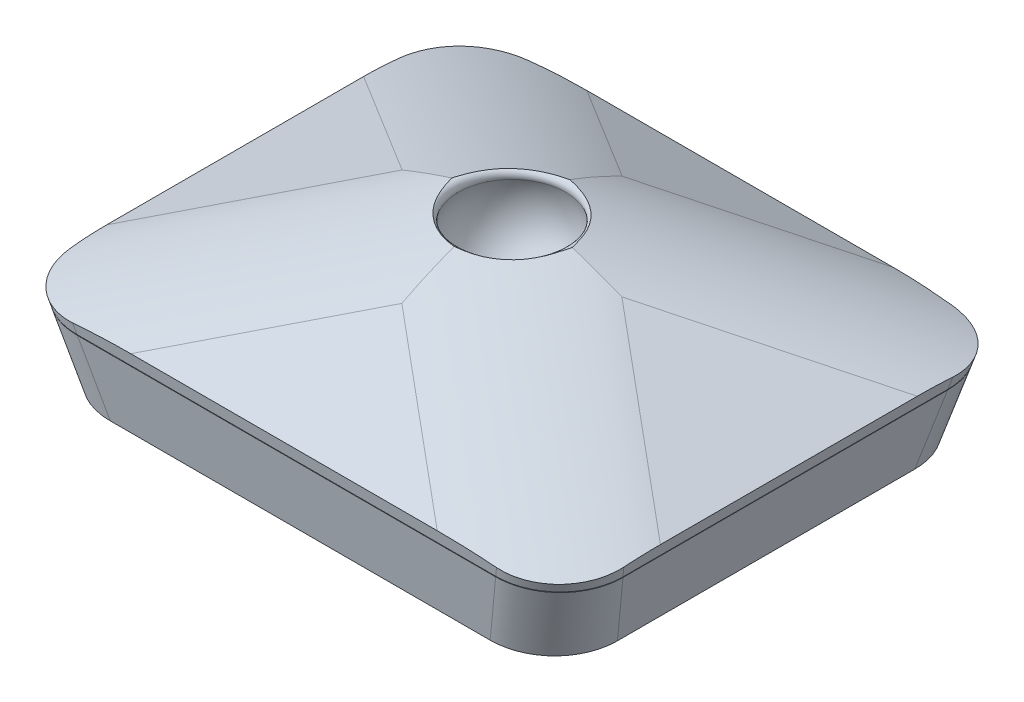
SolidWorks part; units mm, degrees
ref_plane "Front Plane" through (0, 0, 0) normal (0, 0, 1) x (1, 0, 0)
ref_plane "Top Plane" through (0, 0, 0) normal (0, 1, 0) x (1, 0, 0)
ref_plane "Right Plane" through (0, 0, 0) normal (1, 0, 0) x (0, 0, -1)
sketch "Sketch1" plane through (0, 0, 0) normal (0, 1, 0) x (1, 0, 0)
  line L1 (-42.5, 35) -> (42.5, 35)
  line L2 (-42.5, 35) -> (-42.5, -35)
  line L3 (-42.5, -35) -> (42.5, -35)
  line L4 (42.5, 35) -> (42.5, -35)
  line L5 (-42.5, 35) -> (42.5, -35) construction
  line L6 (-42.5, -35) -> (42.5, 35) construction
  point P0 (0, 0)
extrude "Boss-Extrude1" add sketch "Sketch1" along normal blind 26
sketch "Sketch2" plane through (0, 0, 35) normal (0, 0, 1) x (1, 0, 0)
  line L0 (-39, 0) -> (-42.5, 0)
  line L1 (-42.5, 0) -> (42.5, 0) construction
  line L2 (39, 0) -> (42.5, 0)
  line L4 (42.5, 26) -> (42.5, 0) construction
  line L5 (-42.5, 26) -> (-42.5, 0) construction
  line L6 (-42.5, 13) -> (-39, 0)
  line L7 (-42.5, 0) -> (-42.5, 13)
  line L8 (42.5, 13) -> (39, 0)
  line L9 (42.5, 0) -> (42.5, 13)
extrude "Cut-Extrude1" cut sketch "Sketch2" against normal through all
sketch "Sketch3" plane through (0, 0, 35) normal (0, 0, 1) x (1, 0, 0)
  line L0 (-10, 26) -> (-42.5, 13)
  line L1 (-42.5, 26) -> (42.5, 26) construction
  line L3 (-42.5, 13) -> (-42.5, 26)
  line L4 (-42.5, 26) -> (-10, 26)
  line L5 (10, 26) -> (42.5, 13)
  line L6 (42.5, 13) -> (42.5, 26)
  line L7 (42.5, 26) -> (10, 26)
extrude "Cut-Extrude2" cut sketch "Sketch3" against normal through all
sketch "Sketch4" plane through (0, 0, 0) normal (1, 0, 0) x (0, 0, -1)
  line L0 (32.5, 0) -> (35, 13)
  line L1 (35, 0) -> (-35, 0) construction
  line L3 (35, 13) -> (35, 0)
  line L4 (35, 0) -> (32.5, 0)
  line L5 (-32.5, 0) -> (-35, 13)
  line L6 (-35, 13) -> (-35, 0)
  line L7 (-35, 0) -> (-32.5, 0)
extrude "Cut-Extrude3" cut sketch "Sketch4" against normal through all and the other way through all
sketch "Sketch5" plane through (0, 0, 0) normal (1, 0, 0) x (0, 0, -1)
  line L0 (10, 26) -> (35, 13)
  line L1 (35, 26) -> (-35, 26) construction
  line L3 (35, 13) -> (35, 26)
  line L4 (35, 26) -> (10, 26)
  line L5 (-10, 26) -> (-35, 13)
  line L6 (-35, 13) -> (-35, 26)
  line L7 (-35, 26) -> (-10, 26)
extrude "Cut-Extrude4" cut sketch "Sketch5" against normal through all and the other way through all
sketch "Sketch7" plane through (0, 26, 0) normal (0, 1, 0) x (1, 0, 0)
  line L1 (-2.5, 2.5) -> (2.5, 2.5)
  line L2 (-2.5, 2.5) -> (-2.5, -2.5)
  line L3 (-2.5, -2.5) -> (2.5, -2.5)
  line L4 (2.5, 2.5) -> (2.5, -2.5)
  line L5 (-2.5, 2.5) -> (2.5, -2.5) construction
  line L6 (-2.5, -2.5) -> (2.5, 2.5) construction
  point P0 (0, 0)
extrude "Cut-Extrude5" cut sketch "Sketch7" against normal blind 5
sketch "Sketch8" plane through (0, 21, 0) normal (0, 1, 0) x (1, 0, 0)
  line L0 (-17.1014, 0) -> (19.9364, 0) construction
  line L1 (-9, 0) -> (9, 0)
  arc A0 (9, 0) -> (-9, 0) centre (0, 0) ccw
revolve "Cut-Revolve3" cut sketch "Sketch8" angle 360 about L0
fillet "Fillet1" radius 40 4 edges at (26.25, 19.5, -22.5) (-26.25, 19.5, -22.5) (-26.25, 19.5, 22.5) (26.25, 19.5, 22.5)
fillet "Fillet2" radius 10 4 edges at (-40.5078, 5.6003, -33.577) (40.5078, 5.6003, -33.577) (40.5078, 5.6003, 33.577) (-40.5078, 5.6003, 33.577)
fillet "Fillet3" radius 1 1 edges at (0, 26, 7.4833)
sketch "Sketch10" plane through (0, 0, 0) normal (0, -1, 0) x (1, 0, 0)
  line L0 (-29.1523, 31.8032) -> (29.1523, 31.8032)
  line L1 (-38.1307, 22.8167) -> (-38.1307, -22.8167)
  line L2 (29.1523, -31.8032) -> (-29.1523, -31.8032)
  line L3 (38.1307, -22.8167) -> (38.1307, 22.8167)
  arc A0 (-29.1523, 31.8032) -> (-38.1307, 22.8167) centre (-28.6439, 22.3168) ccw
  arc A1 (-38.1307, -22.8167) -> (-29.1523, -31.8032) centre (-28.6439, -22.3168) ccw
  arc A2 (29.1523, -31.8032) -> (38.1307, -22.8167) centre (28.6439, -22.3168) ccw
  arc A3 (38.1307, 22.8167) -> (29.1523, 31.8032) centre (28.6439, 22.3168) ccw
  dimension "D1" = 19
  dimension "D2" = 19
  dimension "D3" = 19
  dimension "D4" = 19
extrude "Boss-Extrude2" add sketch "Sketch10" along normal blind 0.5
sketch "Sketch11" plane through (0, 0, 0) normal (0, 0, 1) x (1, 0, 0)
  line L3 (-47.5, 11.05) -> (47.5, 11.05)
  line L4 (-47.5, 11.05) -> (-47.5, 10.95)
  line L5 (-47.5, 10.95) -> (47.5, 10.95)
  line L6 (47.5, 11.05) -> (47.5, 10.95)
  line L7 (-47.5, 11.05) -> (47.5, 10.95) construction
  line L8 (-47.5, 10.95) -> (47.5, 11.05) construction
extrude "Cut-Extrude7" cut sketch "Sketch11" against normal blind 10 from offset 35
mirror "Mirror1" about plane through (0, 0, 0) normal (0, 0, 1) of "Cut-Extrude7"
sketch "Sketch12" plane through (0, 0, 0) normal (1, 0, 0) x (0, 0, -1)
  line L3 (25, 10.95) -> (-25, 10.95)
  line L4 (25, 10.95) -> (25, 11.05)
  line L5 (25, 11.05) -> (-25, 11.05)
  line L6 (-25, 10.95) -> (-25, 11.05)
  line L7 (25, 10.95) -> (-25, 11.05) construction
  line L8 (25, 11.05) -> (-25, 10.95) construction
extrude "Cut-Extrude8" cut sketch "Sketch12" against normal blind 1 from offset 42.5
mirror "Mirror2" about plane through (0, 0, 0) normal (1, 0, 0) of "Cut-Extrude8"
sketch "Sketch13" plane through (0, -0.5, 0) normal (0, -1, 0) x (1, 0, 0)
  line L4 (-36.25, 3.75) -> (-31.25, 3.75)
  line L5 (-36.25, 3.75) -> (-36.25, -3.75)
  line L6 (-36.25, -3.75) -> (-31.25, -3.75)
  line L7 (-31.25, 3.75) -> (-31.25, -3.75)
  line L8 (-36.25, 3.75) -> (-31.25, -3.75) construction
  line L9 (-36.25, -3.75) -> (-31.25, 3.75) construction
  circle A0 centre (-33.75, 10) radius 2.5
  circle A1 centre (-33.75, -10) radius 2.5
extrude "Cut-Extrude9" cut sketch "Sketch13" against normal blind 4
mirror "Mirror3" about plane through (0, 0, 0) normal (1, 0, 0) of "Cut-Extrude9"
sketch "Sketch14" plane through (0, -0.5, 0) normal (0, -1, 0) x (1, 0, 0)
  line L0 (-30.75, -10) -> (-30.75, 10)
  line L1 (-38.1307, 13.75) -> (-33.2781, 12.9626)
  line L2 (-38.1307, 22.8167) -> (-38.1307, -22.8167) construction
  line L3 (-38.1307, 13.75) -> (-38.1307, -13.75)
  line L4 (-38.1307, -13.75) -> (-33.2695, -12.9612)
  arc A0 (-30.75, 10) -> (-33.2781, 12.9626) centre (-33.75, 10) ccw
  arc A1 (-33.2695, -12.9612) -> (-30.75, -10) centre (-33.75, -10) ccw
extrude "Cut-Extrude10" cut sketch "Sketch14" against normal blind 0.5
mirror "Mirror4" about plane through (0, 0, 0) normal (1, 0, 0) of "Cut-Extrude10"
